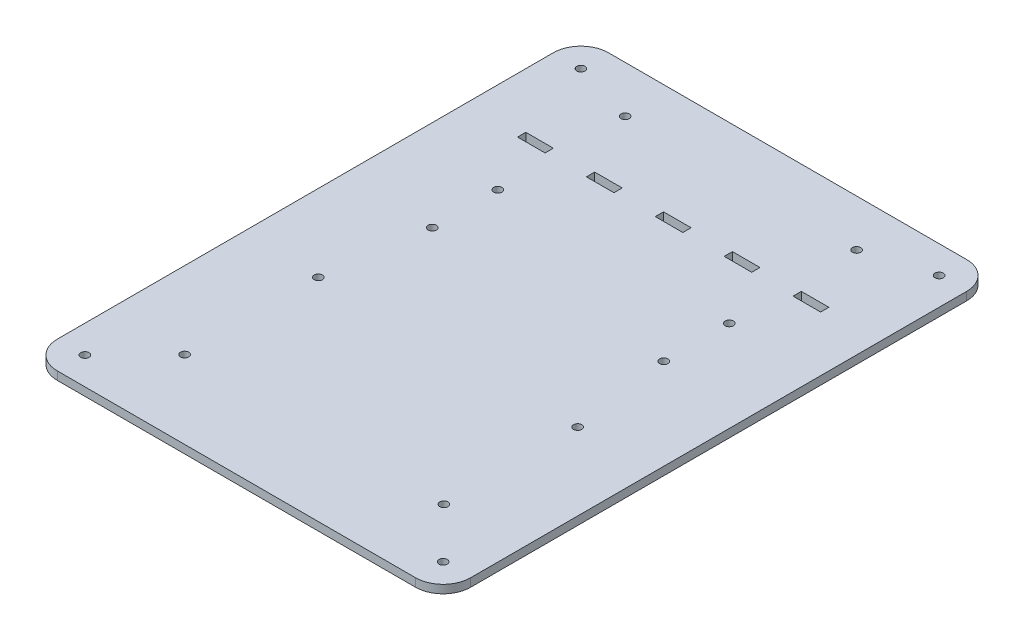
SolidWorks part; units mm, degrees
ref_plane "Спереди" through (0, 0, 0) normal (0, 0, 1) x (1, 0, 0)
ref_plane "Сверху" through (0, 0, 0) normal (0, 1, 0) x (1, 0, 0)
ref_plane "Справа" through (0, 0, 0) normal (1, 0, 0) x (0, 0, -1)
sketch "Эскиз1" plane through (0, 0, 0) normal (0, 1, 0) x (1, 0, 0)
  line L1 (75, -100) -> (-75, -100)
  line L2 (75, -100) -> (75, 100)
  line L3 (75, 100) -> (-75, 100)
  line L4 (-75, -100) -> (-75, 100)
  line L5 (75, -100) -> (-75, 100) construction
  line L6 (75, 100) -> (-75, -100) construction
  point P0 (0, 0)
  dimension "D1" = 200
  dimension "D2" = 150
extrude "Бобышка-Вытянуть1" add sketch "Эскиз1" along normal mid plane 3
fillet "Скругление1" radius 10 4 edges at (-75, 0, -100) (75, 0, -100) (75, 0, 100) (-75, 0, 100)
sketch "Эскиз2" plane through (0, 1.5, 0) normal (0, 1, 0) x (1, 0, 0)
  line L0 (0, 0) -> (0, -33.246) construction
  line L1 (0, 0) -> (-47.6996, 0) construction
  circle A0 centre (-65, 90) radius 1.5
  circle A1 centre (-65, -90) radius 1.5
  circle A2 centre (65, -90) radius 1.5
  circle A3 centre (65, 90) radius 1.5
extrude "Вырез-Вытянуть1" cut sketch "Эскиз2" against normal up to surface (3 mm away) up to face at (0, -1.5, 0)
sketch "Эскиз3" plane through (0, 1.5, 0) normal (0, 1, 0) x (1, 0, 0)
  line L0 (-45, 60) -> (-45, 57)
  line L4 (-55, 57) -> (-55, 60)
  line L5 (-20, 60) -> (-20, 57)
  line L6 (-30, 57) -> (-30, 60)
  line L14 (-45, 60) -> (-55, 60)
  line L15 (-20, 60) -> (-30, 60)
  line L16 (-20, 57) -> (-30, 57)
  line L17 (-45, 57) -> (-55, 57)
  line L19 (5, 60) -> (5, 57)
  line L20 (-5, 57) -> (-5, 60)
  line L23 (5, 60) -> (-5, 60)
  line L24 (5, 57) -> (-5, 57)
  line L27 (30, 60) -> (30, 57)
  line L28 (20, 57) -> (20, 60)
  line L30 (30, 60) -> (20, 60)
  line L31 (30, 57) -> (20, 57)
  line L32 (55, 60) -> (55, 57)
  line L33 (45, 57) -> (45, 60)
  line L34 (55, 60) -> (45, 60)
  line L35 (55, 57) -> (45, 57)
  line L36 (-75, 90) -> (-75, -90) construction
  line L38 (65, 100) -> (-65, 100) construction
  dimension "D1" = 3
  dimension "D2" = 5
  dimension "D3" = 10
  dimension "D4" = 20
  dimension "D5" = 40
extrude "Вырез-Вытянуть2" cut sketch "Эскиз3" against normal up to surface (3 mm away) contours L35 L32 L34 L33 | L31 L27 L30 L28 | L24 L19 L23 L20 | L16 L5 L15 L6 | L17 L0 L14 L4 region at (-50, 1.5, -58.5) region at (-25, 1.5, -58.5) region at (0, 1.5, -58.5) region at (25, 1.5, -58.5) region at (50, 1.5, -58.5) up to face at (65, -1.5, -88.5)
sketch "Sketch1" plane through (0, 1.5, 0) normal (0, 1, 0) x (1, 0, 0)
  circle A0 centre (-47.05, -23.23) radius 1.5
  circle A1 centre (-47.05, -71.77) radius 1.5
  circle A2 centre (47.05, -71.77) radius 1.5
  circle A3 centre (47.05, -23.23) radius 1.5
  circle A4 centre (-42, 36.8614) radius 1.5
  circle A5 centre (42, 36.8614) radius 1.5
  circle A6 centre (42, 13.0614) radius 1.5
  circle A7 centre (-42, 13.0614) radius 1.5
  circle A8 centre (-42, 83.0614) radius 1.5
  circle A9 centre (42, 83.0614) radius 1.5
extrude "Cut-Extrude1" cut sketch "Sketch1" against normal up to next
